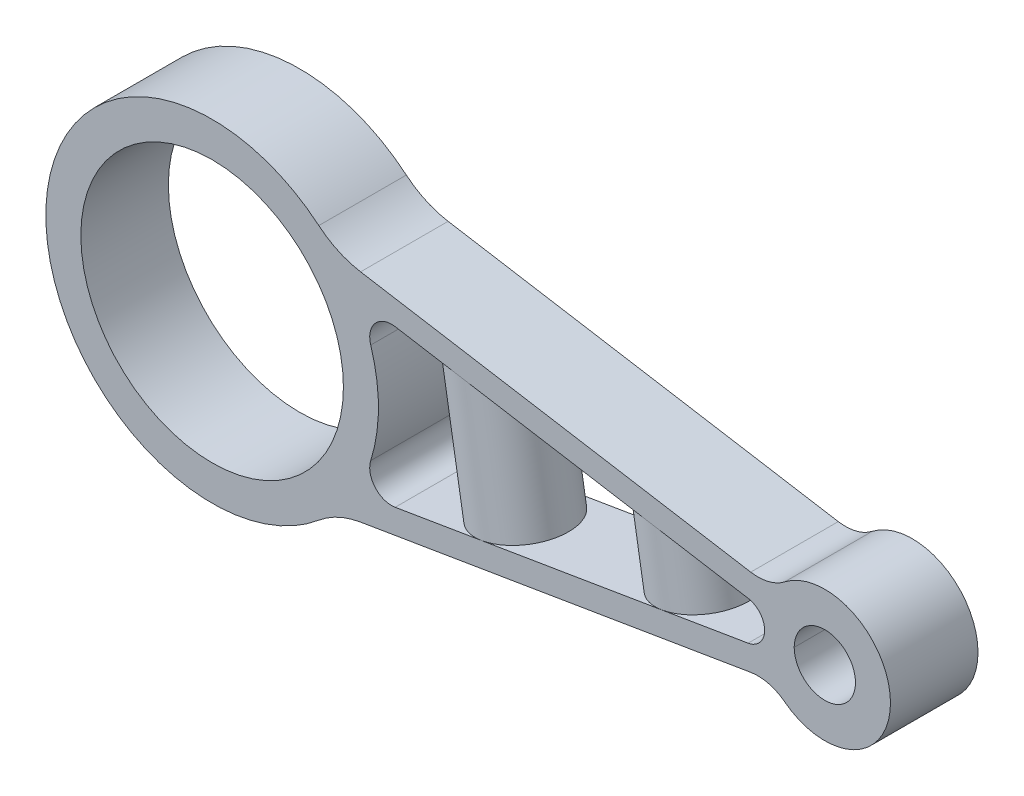
SolidWorks part; units mm, degrees
material "Plain Carbon Steel"
ref_plane "Front Plane" through (0, 0, 0) normal (0, 0, 1) x (1, 0, 0)
ref_plane "Top Plane" through (0, 0, 0) normal (0, 1, 0) x (1, 0, 0)
ref_plane "Right Plane" through (0, 0, 0) normal (1, 0, 0) x (0, 0, -1)
sketch "Sketch1" plane through (0, 0, 0) normal (0, 0, 1) x (1, 0, 0)
  line L0 (-98.8908, 25.7606) -> (1.2375, 9.0844)
  line L2 (-160.0263, 0) -> (142.1007, 0) construction
  line L4 (1.2375, -9.0844) -> (-98.8908, -25.7606)
  circle A0 centre (-126.8263, 0) radius 30
  arc A1 (-98.8908, 25.7606) -> (-98.8908, -25.7606) centre (-126.8263, 0) ccw
  circle A2 centre (13.1737, 0) radius 7
  arc A3 (1.2375, -9.0844) -> (1.2375, 9.0844) centre (13.1737, 0) ccw
  dimension "D2" = 60
  dimension "D3" = 76
  dimension "D4" = 14
  dimension "D5" = 30
  dimension "D1" = 140
extrude "Boss-Extrude1" add sketch "Sketch1" along normal mid plane 20
fillet "Fillet1" radius 20 1 edges at (-98.8908, 25.7606, 0)
fillet "Fillet2" radius 10 1 edges at (1.2375, 9.0844, 0)
fillet "Fillet3" radius 20 1 edges at (-98.8908, -25.7606, 0)
fillet "Fillet4" radius 10 1 edges at (1.2375, -9.0844, 0)
sketch "Sketch2" plane through (0, 0, 10) normal (0, 0, 1) x (1, 0, 0)
  line L0 (-84.9977, -17.871) -> (-4.3479, -4.4389)
  line L1 (-84.9977, 17.871) -> (-4.3479, 4.4389)
  line L2 (0, 0) -> (-126.8263, 0) construction
  line L3 (-3.7575, 9.9163) -> (-92.9032, 24.7634) construction
  line L4 (-92.9032, -24.7634) -> (-3.7575, -9.9163) construction
  arc A6 (-4.3479, 4.4389) -> (-4.3479, -4.4389) centre (-5.0872, 0) cw
  arc A7 (-84.9977, 17.871) -> (-90.5874, 11.4344) centre (-85.8192, 12.9389) ccw
  arc A8 (-84.9977, -17.871) -> (-90.5874, -11.4344) centre (-85.8192, -12.9389) cw
  arc A9 (-90.5874, 11.4344) -> (-90.5874, -11.4344) centre (-126.8263, 0) cw
  circle A10 centre (-126.8263, 0) radius 30 construction
  dimension "D1" = 4.5
  dimension "D2" = 5
  dimension "D3" = 5.5
  dimension "D4" = 8
extrude "Cut-Extrude3" cut sketch "Sketch2" against normal through all contours L1 A6 L0 A8 A9 A7
split line "Split Line1"
sketch "Sketch3" plane through (0.602, -3.6145, 0) normal (-0.1643, 0.9864, 0) x (0.9864, 0.1643, 0)
  line L0 (-86.7788, 10) -> (-5.018, 10) construction
  line L1 (-86.7788, -10) -> (-5.018, -10) construction
  line L3 (-86.7788, 10) -> (-86.7788, -10) construction
  line L4 (-5.018, 10) -> (-5.018, -10) construction
  circle A0 centre (-66.7788, 0) radius 10
  circle A1 centre (-25.018, 0) radius 10
  dimension "D1" = 20
  dimension "D2" = 20
extrude "Boss-Extrude2" add sketch "Sketch3" along normal up to next
